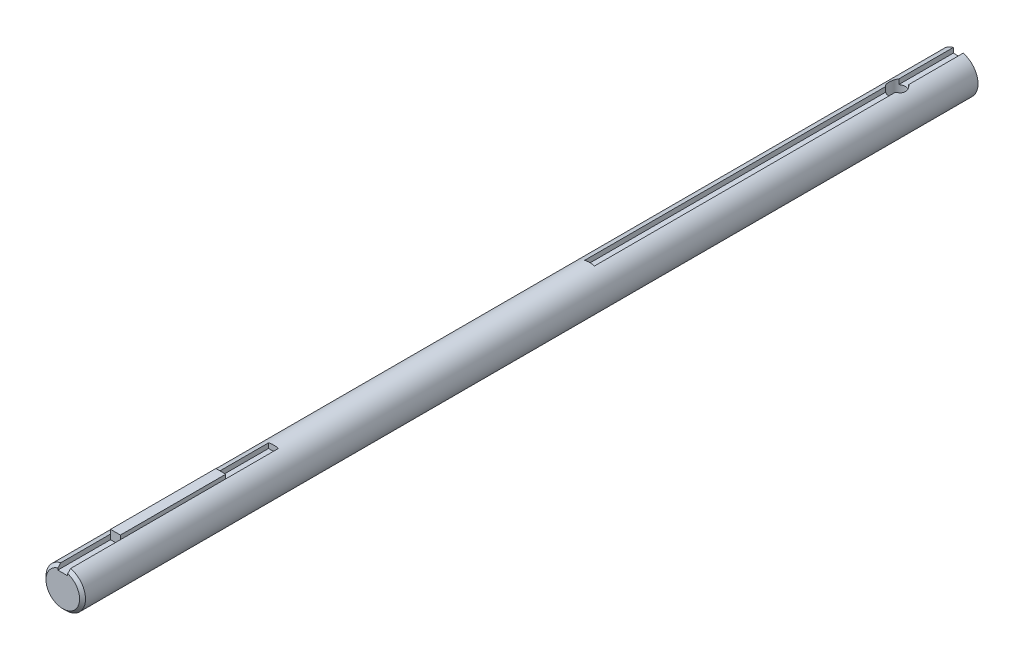
SolidWorks part; units mm, degrees
ref_plane "Front Plane" through (0, 0, 0) normal (0, 0, 1) x (1, 0, 0)
ref_plane "Top Plane" through (0, 0, 0) normal (0, 1, 0) x (1, 0, 0)
ref_plane "Right Plane" through (0, 0, 0) normal (1, 0, 0) x (0, 0, -1)
sketch "Sketch1" plane through (0, 0, 0) normal (0, 0, 1) x (1, 0, 0)
  line L0 (-2.3813, 6.8413) -> (2.3813, 6.8413)
  line L1 (-2.3813, 6.8413) -> (-2.3812, 9.2225)
  line L2 (2.3813, 6.8413) -> (2.3812, 9.2225)
  line L3 (-2.3812, 11.1792) -> (2.3812, 11.1792)
  line L4 (-2.3812, 11.1792) -> (-2.3812, 9.2225)
  line L5 (2.3812, 11.1792) -> (2.3812, 9.2225)
  circle A0 centre (0, 0) radius 9.525
  circle A1 centre (0, 0) radius 11.43 construction
  point P5 (0, 6.8413)
  point P11 (0, 9.525)
  dimension "Diameter" = 19.05
  dimension "D1" = 22.86
  dimension "Keyway Width" = 4.7625
  dimension "Keyway Depth" = 2.3813
  dimension "D2" = 4.7625
sketch "Sketch2" plane through (0, 0, 0) normal (1, 0, 0) x (0, 0, -1)
  line L0 (-304.8, 9.525) -> (304.8, 9.525)
  point P2 (-203.2, 9.525)
  point P3 (-50.8, 9.525)
  point P4 (-38.1, 9.525)
  point P5 (-279.4, 9.525)
  point P6 (-228.6, 9.525)
  point P7 (279.4, 9.525)
  point P8 (177.8, 9.525)
  point P9 (-171.45, 9.525)
  point P10 (171.45, 9.525)
  point P11 (-50.8, 9.525)
  point P12 (304.8, 9.525)
  point P13 (-63.5, 9.525)
  dimension "Length" = 609.6
  dimension "Key 1 Length" = 50.8
  dimension "D2" = 25.4
  dimension "Key 2 Length" = 101.6
  dimension "D3" = 133.35
  dimension "D4" = 133.35
  dimension "D5" = 12.7
  dimension "D6" = 12.7
sketch "Sketch3" plane through (0, 0, 0) normal (0, 0, 1) x (1, 0, 0)
  circle A0 centre (0, 0) radius 9.525 construction
  circle A1 centre (0, 0) radius 9.525
extrude "Boss-Extrude1" add sketch "Sketch3" along normal mid plane 609.6
chamfer "Chamfer1" distance 1.4287 angle 45 2 edges at (9.525, 0, -304.8) (9.525, 0, 304.8)
sketch "Sketch5" plane through (0, 0, 304.8) normal (0, 0, 1) x (1, 0, 0)
  line L0 (-2.3812, 11.1792) -> (2.3812, 11.1792) construction
  line L1 (2.3812, 11.1792) -> (2.3812, 9.2225) construction
  line L2 (2.3813, 6.8413) -> (2.3812, 9.2225) construction
  line L3 (-2.3813, 6.8413) -> (2.3813, 6.8413) construction
  line L4 (-2.3813, 6.8413) -> (-2.3812, 9.2225) construction
  line L5 (-2.3812, 11.1792) -> (-2.3812, 9.2225) construction
  line L6 (-2.3812, 11.1792) -> (2.3812, 11.1792)
  line L7 (2.3812, 11.1792) -> (2.3812, 9.2225)
  line L8 (2.3813, 6.8413) -> (2.3812, 9.2225)
  line L9 (-2.3813, 6.8413) -> (2.3813, 6.8413)
  line L10 (-2.3813, 6.8413) -> (-2.3812, 9.2225)
  line L11 (-2.3812, 11.1792) -> (-2.3812, 9.2225)
extrude "Cut-Extrude1" cut sketch "Sketch5" against normal up to vertex (101.6 mm away) up to point (0, 9.525, 203.2)
sketch "Sketch6" plane through (0, 0, -304.8) normal (0, 0, -1) x (-1, 0, 0)
  line L6 (2.3812, 11.1792) -> (-2.3812, 11.1792)
  line L7 (-2.3812, 11.1792) -> (-2.3812, 9.2225)
  line L8 (-2.3812, 9.2225) -> (-2.3813, 6.8413)
  line L9 (-2.3813, 6.8413) -> (2.3813, 6.8413)
  line L10 (2.3813, 6.8413) -> (2.3812, 9.2225)
  line L11 (2.3812, 9.2225) -> (2.3812, 11.1792)
  line L12 (2.3812, 11.1792) -> (-2.3812, 11.1792)
  line L13 (-2.3812, 11.1792) -> (-2.3812, 9.2225)
  line L14 (-2.3812, 9.2225) -> (-2.3813, 6.8413)
  line L15 (-2.3813, 6.8413) -> (2.3813, 6.8413)
  line L16 (2.3813, 6.8413) -> (2.3812, 9.2225)
  line L17 (2.3812, 9.2225) -> (2.3812, 11.1792)
  dimension "D1" = 0
extrude "Cut-Extrude2" cut sketch "Sketch6" against normal up to vertex (355.6 mm away) up to point (0, 9.525, 50.8)
ref_plane "Plane1" through (0, 0, 279.4) normal (0, 0, 1) x (1, 0, 0)
sketch "Sketch7" plane through (0, 0, 279.4) normal (0, 0, 1) x (1, 0, 0)
  line L0 (-2.3812, 11.1792) -> (-2.3812, 9.2225) construction
  line L1 (-2.3813, 6.8413) -> (-2.3812, 9.2225) construction
  line L2 (-2.3813, 6.8413) -> (2.3813, 6.8413) construction
  line L3 (2.3813, 6.8413) -> (2.3812, 9.2225) construction
  line L4 (2.3812, 11.1792) -> (2.3812, 9.2225) construction
  line L5 (-2.3812, 11.1792) -> (2.3812, 11.1792) construction
  line L6 (-2.3812, 11.1792) -> (-2.3812, 9.2225)
  line L7 (-2.3813, 6.8413) -> (-2.3812, 9.2225)
  line L8 (-2.3813, 6.8413) -> (2.3813, 6.8413)
  line L9 (2.3813, 6.8413) -> (2.3812, 9.2225)
  line L10 (2.3812, 11.1792) -> (2.3812, 9.2225)
  line L11 (-2.3812, 11.1792) -> (2.3812, 11.1792)
extrude "Boss-Extrude2" add sketch "Sketch7" against normal up to vertex (50.8 mm away) up to point (0, 9.525, 228.6)
ref_plane "Plane2" through (0, 0, -279.4) normal (0, 0, 1) x (1, 0, 0)
sketch "Sketch8" plane through (0, 0, -279.4) normal (0, 0, 1) x (1, 0, 0)
  line L0 (-2.3812, 11.1792) -> (-2.3812, 9.2225) construction
  line L1 (-2.3813, 6.8413) -> (-2.3812, 9.2225) construction
  line L2 (-2.3813, 6.8413) -> (2.3813, 6.8413) construction
  line L3 (2.3813, 6.8413) -> (2.3812, 9.2225) construction
  line L4 (2.3812, 11.1792) -> (2.3812, 9.2225) construction
  line L5 (-2.3812, 11.1792) -> (2.3812, 11.1792) construction
  line L6 (-2.3812, 11.1792) -> (-2.3812, 9.2225)
  line L7 (-2.3813, 6.8413) -> (-2.3812, 9.2225)
  line L8 (-2.3813, 6.8413) -> (2.3813, 6.8413)
  line L9 (2.3813, 6.8413) -> (2.3812, 9.2225)
  line L10 (2.3812, 11.1792) -> (2.3812, 9.2225)
  line L11 (-2.3812, 11.1792) -> (2.3812, 11.1792)
extrude "Boss-Extrude3" add sketch "Sketch8" along normal up to vertex (101.6 mm away) up to point (0, 9.525, -177.8)
sketch "Sketch9" plane through (0, 0, 0) normal (0, 1, 0) x (1, 0, 0)
  line L0 (2.3813, 304.8) -> (-2.3813, 304.8) construction
  line L1 (0, 97.536) -> (-9.525, 97.536) construction
  line L2 (-9.525, 303.3712) -> (-9.525, -303.3713) construction
  line L3 (0, 97.536) -> (9.525, 97.536) construction
  line L4 (9.525, -303.3713) -> (9.525, 303.3712) construction
  circle A1 centre (0, 97.536) radius 3.9687
  point P0 (0, 97.536)
  dimension "D2" = 7.9375
  dimension "D1" = 207.264
extrude "Cut-Extrude3" cut sketch "Sketch9" against normal through all both and the other way through all
sketch "Sketch10" plane through (0, 0, -304.8) normal (0, 0, -1) x (-1, 0, 0)
  circle A0 centre (0, 0) radius 15.2987
extrude "Cut-Extrude4" cut sketch "Sketch10" against normal blind 177.8
equation "\"D1@Sketch1\"=\"Diameter@Sketch1\"*1.2"
equation "\"D1@Boss-Extrude1\"=\"length@sketch2\""
equation "\"D1@Chamfer1\"=\"Diameter@Sketch1\"*0.075"
equation "\"D4@Sketch2\"=\"D3@Sketch2\""
equation "\"D6@Sketch2\"=\"D5@Sketch2\""
